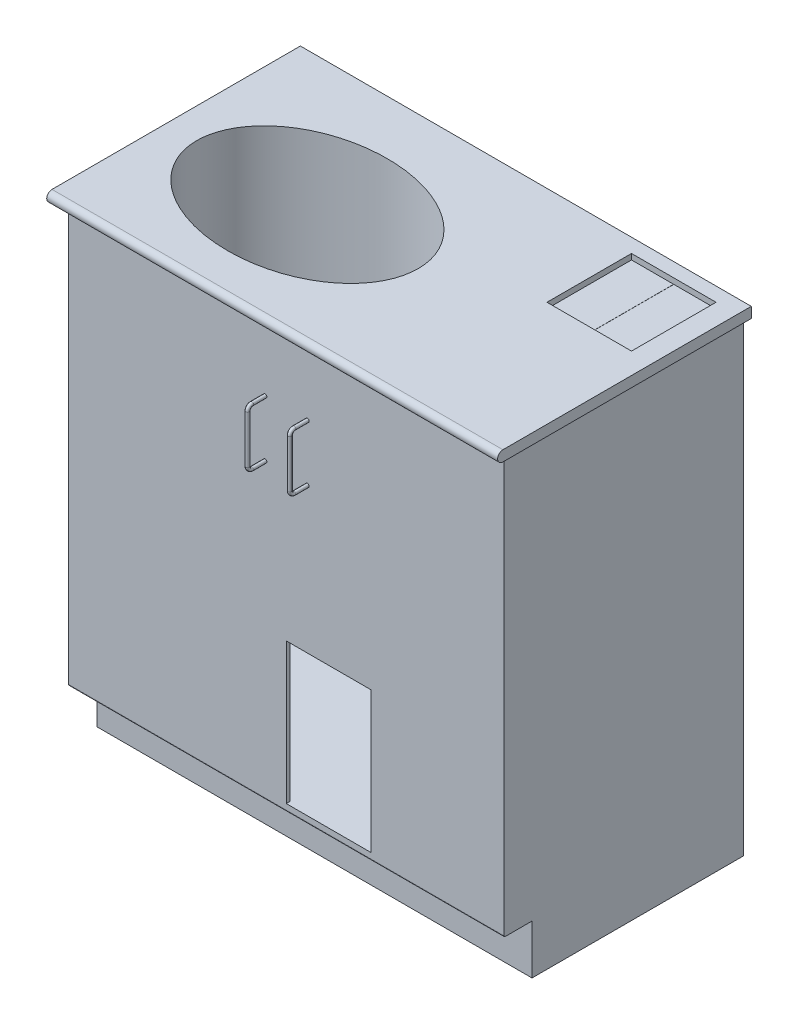
SolidWorks part; units mm, degrees
other "Camera1"
other "Camera2"
ref_plane "Front Plane" through (0, 0, 0) normal (0, 0, 1) x (1, 0, 0)
ref_plane "Top Plane" through (0, 0, 0) normal (0, 1, 0) x (1, 0, 0)
ref_plane "Right Plane" through (0, 0, 0) normal (1, 0, 0) x (0, 0, -1)
ref_plane "Ground Plane" through (0, 0, 0) normal (0, 1, 0) x (1, 0, 0)
sketch "Sketch2" plane through (0, 0, 0) normal (0, 1, 0) x (1, 0, 0)
  line L1 (0, 0) -> (812.8, 0)
  line L2 (0, 0) -> (0, 457.2)
  line L3 (0, 457.2) -> (812.8, 457.2)
  line L4 (812.8, 0) -> (812.8, 457.2)
  dimension "D1" = 812.8
  dimension "D2" = 457.2
extrude "Boss-Extrude1" add sketch "Sketch2" along normal blind 865.124
ref_plane "Wall Plane" through (0, 0, -457.2) normal (0, 0, -1) x (-1, 0, 0)
ref_plane "Faucet Plane" through (254, 0, 0) normal (-1, 0, 0) x (0, 0, 1)
ref_plane "Central Plane" through (406.4, 0, 0) normal (-1, 0, 0) x (0, 0, 1)
ref_plane "Piping Alignment" through (203.2, 0, 0) normal (-1, 0, 0) x (0, 0, 1)
sketch "Sketch28" plane through (0, 0, -457.2) normal (0, 0, -1) x (-1, 0, 0)
  line L1 (-203.2, -251.46) -> (-203.2, 251.46) construction
  circle A0 centre (-203.2, 744.0072) radius 6.35
  dimension "D1" = 0
extrude "Boss-Extrude4" add sketch "Sketch28" along normal blind 50.8
sketch "Sketch30" plane through (0, 0, -457.2) normal (0, 0, -1) x (-1, 0, 0)
  line L1 (-203.2, -251.46) -> (-203.2, 251.46) construction
  circle A0 centre (-203.2, 575.1895) radius 19.05
  dimension "D1" = 0
extrude "Boss-Extrude5" add sketch "Sketch30" along normal blind 50.8
sketch "Sketch31" plane through (812.8, 0, 0) normal (1, 0, 0) x (0, 0, -1)
  line L0 (0, 865.124) -> (0, 0) construction
  line L1 (0, 846.074) -> (25.4, 846.074)
  line L2 (0, 846.074) -> (0, 0)
  line L3 (0, 0) -> (25.4, 0)
  line L4 (25.4, 846.074) -> (25.4, 0)
  line L5 (0, 0) -> (457.2, 0) construction
  line L6 (0, 865.124) -> (457.2, 865.124) construction
  dimension "D1" = 25.4
  dimension "D2" = 19.05
extrude "Cut-Extrude1" cut sketch "Sketch31" against normal through all both and the other way through all
ref_plane "Plane2" through (368.3, 0, 0) normal (-1, 0, 0) x (0, 0, 1)
ref_plane "Plane3" through (444.5, 0, 0) normal (-1, 0, 0) x (0, 0, 1)
sketch "Sketch34" plane through (368.3, 0, 0) normal (-1, 0, 0) x (0, 0, 1)
  line L0 (-25.4, 719.074) -> (-1.27, 719.074)
  line L1 (-25.4, 0) -> (-25.4, 846.074) construction
  line L2 (6.35, 711.454) -> (6.35, 625.094)
  line L3 (-1.27, 617.474) -> (-25.4, 617.474)
  line L4 (-25.4, 846.074) -> (0, 846.074) construction
  arc A0 (-1.27, 719.074) -> (6.35, 711.454) centre (-1.27, 711.454) cw
  arc A1 (6.35, 625.094) -> (-1.27, 617.474) centre (-1.27, 625.094) cw
  dimension "D2" = 7.62
  dimension "D3" = 7.62
  dimension "D1" = 31.75
  dimension "D4" = 101.6
  dimension "D5" = 127
sweep "Sweep2" add path "Sketch34" circular profile diameter 6.35 parameters "D3"=6.35
mirror "Mirror1" about plane through (406.4, 0, 0) normal (-1, 0, 0) of "Sweep2"
fillet "Fillet1" 2 edges at (406.4, 865.124, 0) (406.4, 846.074, 0) type full round first side face at (406.4, 865.124, -228.6) second side face at (406.4, 846.074, -12.7) middle face at (406.4, 855.599, 0)
sketch "Sketch160" plane through (0, 0, -25.4) normal (0, 0, 1) x (1, 0, 0)
  line L0 (0, 846.074) -> (812.8, 846.074) construction
  line L1 (812.8, 0) -> (798.576, 0)
  line L2 (812.8, 0) -> (812.8, 846.074)
  line L3 (812.8, 846.074) -> (798.576, 846.074)
  line L4 (798.576, 0) -> (798.576, 846.074)
  line L5 (0, 0) -> (812.8, 0) construction
  line L6 (0, 846.074) -> (14.224, 846.074)
  line L7 (0, 846.074) -> (0, 0)
  line L8 (0, 0) -> (14.224, 0)
  line L9 (14.224, 846.074) -> (14.224, 0)
  dimension "D1" = 14.224
  dimension "D2" = 14.224
extrude "Cut-Extrude2" cut sketch "Sketch160" against normal through all both and the other way through all
ref_axis "Axis - Drain" through (203.2, 575.1895, -508) along (0, 0, 1)
ref_axis "Axis - Water" through (203.2, 744.0072, -508) along (0, 0, 1)
sketch "Sketch163" plane through (0, 0, -25.4) normal (0, 0, 1) x (1, 0, 0)
  line L0 (14.224, 0) -> (798.576, 0) construction
  line L1 (406.4, 355.6) -> (558.8, 355.6)
  line L2 (406.4, 355.6) -> (406.4, 101.6)
  line L3 (406.4, 101.6) -> (558.8, 101.6)
  line L4 (558.8, 355.6) -> (558.8, 101.6)
  line L5 (812.8, 846.074) -> (812.8, 0) construction
  dimension "D1" = 101.6
  dimension "D2" = 254
  dimension "D3" = 152.4
  dimension "D4" = 254
extrude "Cut-Extrude4" cut sketch "Sketch163" against normal blind 406.4
ref_plane "Plane4" through (0, 0, -31.75) normal (0, 0, 1) x (1, 0, 0)
sketch "Sketch193" plane through (0, 0, -31.75) normal (0, 0, 1) x (1, 0, 0)
  line L0 (798.576, 0) -> (798.576, 846.074) construction
  line L1 (20.574, 101.6) -> (792.226, 101.6)
  line L2 (20.574, 101.6) -> (20.574, 411.9299)
  line L3 (20.574, 411.9299) -> (792.226, 411.9299)
  line L4 (792.226, 101.6) -> (792.226, 411.9299)
  line L5 (14.224, 846.074) -> (14.224, 0) construction
  line L9 (406.4, 101.6) -> (558.8, 101.6) construction
  dimension "D1" = 6.35
  dimension "D2" = 6.35
extrude "Cut-Extrude10" cut sketch "Sketch193" against normal blind 419.1
sketch "Sketch195" plane through (0, 865.124, 0) normal (0, 1, 0) x (1, 0, 0)
  line L0 (812.8, 457.2) -> (0, 457.2) construction
  line L1 (774.7, 431.8) -> (622.3, 431.8)
  line L2 (774.7, 431.8) -> (774.7, 279.4)
  line L3 (774.7, 279.4) -> (622.3, 279.4)
  line L4 (622.3, 431.8) -> (622.3, 279.4)
  line L5 (812.8, 9.525) -> (812.8, 457.2) construction
  dimension "D1" = 152.4
  dimension "D2" = 152.4
  dimension "D3" = 25.4
  dimension "D4" = 38.1
extrude "Cut-Extrude12" cut sketch "Sketch195" against normal blind 659.13
ref_plane "Plane5" through (0, 852.424, 0) normal (0, 1, 0) x (1, 0, 0)
sketch "Sketch196" plane through (0, 852.424, 0) normal (0, 1, 0) x (1, 0, 0)
  line L1 (622.3, 431.8) -> (698.246, 431.8)
  line L2 (622.3, 431.8) -> (622.3, 279.4)
  line L3 (622.3, 279.4) -> (698.246, 279.4)
  line L4 (698.246, 431.8) -> (698.246, 279.4)
  dimension "D1" = 75.946
extrude "Boss-Extrude13" add sketch "Sketch196" along normal blind 2.54
sketch "Sketch197" plane through (0, 852.424, 0) normal (0, 1, 0) x (1, 0, 0)
  line L0 (622.3, 279.4) -> (774.7, 279.4) construction
  line L1 (774.7, 431.8) -> (698.5, 431.8)
  line L2 (774.7, 431.8) -> (774.7, 279.4)
  line L3 (774.7, 279.4) -> (698.5, 279.4)
  line L4 (698.5, 431.8) -> (698.5, 279.4)
extrude "Boss-Extrude14" add sketch "Sketch197" along normal blind 2.54
sketch "Sketch206" plane through (0, 865.124, 0) normal (0, 1, 0) x (1, 0, 0)
  ellipse E0 centre (254, 215.9) end of major axis (54.2175, 215.9) minor radius 143.8906
extrude "Cut-Extrude13" cut sketch "Sketch206" against normal up to next
sketch "Sketch211" plane through (0, 0, -25.4) normal (0, 0, 1) x (1, 0, 0)
  line L0 (798.576, 0) -> (798.576, 846.074) construction
  line L1 (14.224, 0) -> (798.576, 0)
  line L2 (14.224, 0) -> (14.224, 88.9)
  line L3 (14.224, 88.9) -> (798.576, 88.9)
  line L4 (798.576, 0) -> (798.576, 88.9)
  line L5 (406.4, 101.6) -> (558.8, 101.6) construction
  dimension "D1" = 12.7
extrude "Cut-Extrude14" cut sketch "Sketch211" against normal blind 50.8
fillet "Fillet2" radius 2.54 1 edges at (406.4, 88.9, -25.4)
sketch "Sketch212" plane through (0, 865.124, 0) normal (0, 1, 0) x (1, 0, 0)
  line L0 (453.7825, 215.9) -> (54.2175, 215.9)
  line L1 (254, 359.7906) -> (254, 72.0094)
  ellipse E0 centre (254, 215.9) end of major axis (54.2175, 215.9) minor radius 143.8906 construction
ref_plane "Plane6" through (254, 0, 0) normal (-1, 0, 0) x (0, 0, 1)
ref_plane "Plane7" through (0, 0, -215.9) normal (0, 0, 1) x (1, 0, 0)
ref_axis "SinkMount" through (254, 850.7349, -215.9) along (0, 1, 0)
